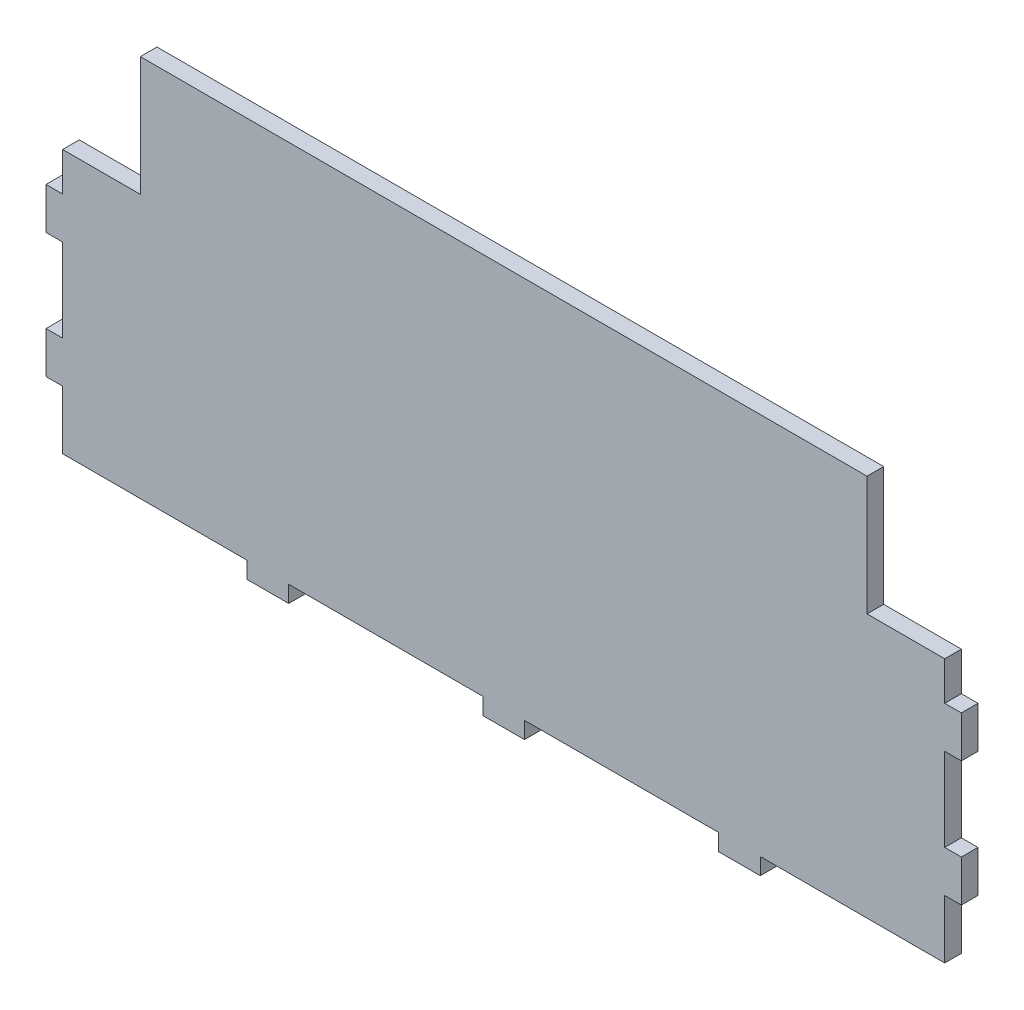
SolidWorks part; units mm, degrees
ref_plane "Plan de face" through (0, 0, 0) normal (0, 0, 1) x (1, 0, 0)
ref_plane "Plan de dessus" through (0, 0, 0) normal (0, 1, 0) x (1, 0, 0)
ref_plane "Plan de droite" through (0, 0, 0) normal (1, 0, 0) x (0, 0, -1)
sketch "Esquisse1" plane through (0, 0, 0) normal (0, 0, 1) x (1, 0, 0)
  line L0 (-159, 37.4465) -> (-131, 37.4465)
  line L1 (0, 102.0551) -> (0, -193.4247) construction
  line L2 (-159, 37.4465) -> (-159, -57.5535)
  line L3 (-159, -57.5535) -> (159, -57.5535)
  line L4 (159, 37.4465) -> (159, -57.5535)
  line L6 (131, 37.4465) -> (131, 80.4465)
  line L7 (131, 80.4465) -> (-131, 80.4465)
  line L8 (-131, 37.4465) -> (-131, 80.4465)
  line L9 (159, 37.4465) -> (131, 37.4465)
  dimension "D1" = 95
  dimension "D2" = 28
  dimension "D3" = 28
  dimension "D4" = 95
  dimension "D6" = 262
  dimension "D7" = 138
  dimension "D5" = 159
  dimension "D8" = 318
extrude "Boss.-Extru.1" add sketch "Esquisse1" along normal blind 6
sketch "Esquisse2" plane through (0, 0, 6) normal (0, 0, 1) x (1, 0, 0)
  line L0 (-159, -57.5535) -> (159, -57.5535) construction
  line L1 (-92.5, -57.5535) -> (-77.5, -57.5535)
  line L2 (-92.5, -57.5535) -> (-92.5, -63.5535)
  line L3 (-92.5, -63.5535) -> (-77.5, -63.5535)
  line L4 (-77.5, -57.5535) -> (-77.5, -63.5535)
  line L5 (-159, 37.4465) -> (-159, -57.5535) construction
  line L6 (-7.5, -57.5535) -> (7.5, -57.5535)
  line L7 (-7.5, -57.5535) -> (-7.5, -63.5535)
  line L8 (-7.5, -63.5535) -> (7.5, -63.5535)
  line L9 (7.5, -57.5535) -> (7.5, -63.5535)
  line L10 (77.5, -57.5535) -> (92.5, -57.5535)
  line L11 (77.5, -57.5535) -> (77.5, -63.5535)
  line L12 (77.5, -63.5535) -> (92.5, -63.5535)
  line L13 (92.5, -57.5535) -> (92.5, -63.5535)
  line L15 (0, 107.6082) -> (0, -117.4775) construction
  line L16 (-131, 37.4465) -> (-159, 37.4465) construction
  line L17 (-159, 23.5365) -> (-165, 23.5365)
  line L18 (-159, 23.5365) -> (-159, 8.5365)
  line L19 (-159, 8.5365) -> (-165, 8.5365)
  line L20 (-165, 23.5365) -> (-165, 8.5365)
  line L21 (-159, -21.4635) -> (-165, -21.4635)
  line L22 (-159, -21.4635) -> (-159, -36.4635)
  line L23 (-159, -36.4635) -> (-165, -36.4635)
  line L24 (-165, -21.4635) -> (-165, -36.4635)
  line L25 (165, -21.4635) -> (165, -36.4635)
  line L26 (159, -36.4635) -> (165, -36.4635)
  line L27 (159, -21.4635) -> (159, -36.4635)
  line L28 (159, -21.4635) -> (165, -21.4635)
  line L29 (165, 23.5365) -> (165, 8.5365)
  line L30 (159, 8.5365) -> (165, 8.5365)
  line L31 (159, 23.5365) -> (159, 8.5365)
  line L32 (159, 23.5365) -> (165, 23.5365)
  dimension "D1" = 66.5
  dimension "D2" = 70
  dimension "D3" = 15
  dimension "D4" = 15
  dimension "D5" = 70
  dimension "D6" = 15
  dimension "D7" = 6
  dimension "D8" = 6
  dimension "D9" = 6
  dimension "D10" = 6
  dimension "D11" = 13.91
  dimension "D12" = 15
  dimension "D13" = 30
  dimension "D14" = 15
extrude "Boss.-Extru.2" add sketch "Esquisse2" against normal blind 6
equation "\"D5@Esquisse1\"=\"D8@Esquisse1\"/2"
